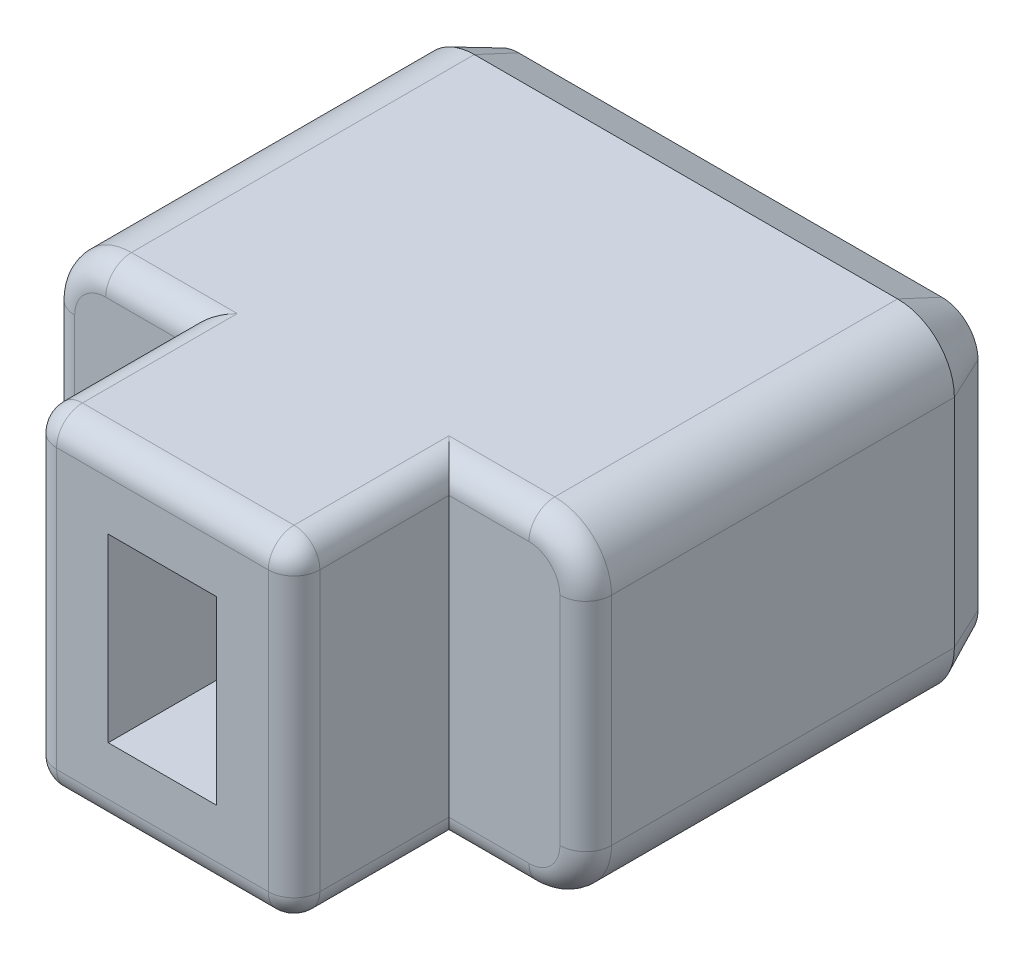
SolidWorks part; units mm, degrees
ref_plane "Plan de face" through (0, 0, 0) normal (0, 0, 1) x (1, 0, 0)
ref_plane "Plan de dessus" through (0, 0, 0) normal (0, 1, 0) x (1, 0, 0)
ref_plane "Plan de droite" through (0, 0, 0) normal (1, 0, 0) x (0, 0, -1)
sketch "Esquisse2" plane through (0, 0, 0) normal (0, 0, 1) x (1, 0, 0)
  line L1 (1.1, 0) -> (9.3, 0)
  line L2 (0, 1.1) -> (0, 5.3)
  line L3 (1.1, 6.4) -> (9.3, 6.4)
  line L4 (10.4, 1.1) -> (10.4, 5.3)
  arc A0 (9.3, 6.4) -> (10.4, 5.3) centre (9.3, 5.3) cw
  arc A1 (9.3, 0) -> (10.4, 1.1) centre (9.3, 1.1) ccw
  arc A2 (1.1, 0) -> (0, 1.1) centre (1.1, 1.1) cw
  arc A3 (0, 5.3) -> (1.1, 6.4) centre (1.1, 5.3) cw
  point P7 (10.4, 6.4)
  point P12 (0, 0)
  point P15 (0, 6.4)
  dimension "D3" = 1.1
  dimension "D1" = 10.4
  dimension "D2" = 6.4
extrude "Boss.-Extru.1" add sketch "Esquisse2" along normal blind 11
sketch "Esquisse3" plane through (0, 0, 11) normal (0, 0, 1) x (1, 0, 0)
  line L0 (0, 5.3) -> (0, 1.1) construction
  line L1 (4.15, 4.95) -> (6.25, 4.95)
  line L2 (4.15, 4.95) -> (4.15, 1.45)
  line L3 (4.15, 1.45) -> (6.25, 1.45)
  line L4 (6.25, 4.95) -> (6.25, 1.45)
  line L5 (10.4, 1.1) -> (10.4, 5.3) construction
  line L6 (9.3, 6.4) -> (1.1, 6.4) construction
  line L7 (1.1, 0) -> (9.3, 0) construction
  dimension "D1" = 2.1
  dimension "D2" = 3.5
  dimension "D3" = 4.15
  dimension "D4" = 4.15
  dimension "D5" = 1.45
  dimension "D6" = 1.45
extrude "Enlèv. mat.-Extru.1" cut sketch "Esquisse3" against normal blind 3
sketch "Esquisse4" plane through (0, 0, 11) normal (0, 0, 1) x (1, 0, 0)
  line L0 (2.65, 6.4) -> (2.65, 0)
  line L1 (9.3, 6.4) -> (1.1, 6.4) construction
  line L2 (1.1, 0) -> (9.3, 0) construction
  line L3 (2.65, 0) -> (7.75, 0)
  line L4 (7.75, 0) -> (7.75, 6.4)
  line L5 (7.75, 6.4) -> (2.65, 6.4)
  line L6 (4.15, 4.95) -> (4.15, 1.45) construction
  line L7 (6.25, 1.45) -> (6.25, 4.95) construction
  dimension "D1" = 1.5
  dimension "D2" = 1.5
extrude "Enlèv. mat.-Extru.2" cut sketch "Esquisse4" against normal blind 3 flip side to cut
fillet "Congé1" radius 0.5 18 edges at (8.525, 0, 8) (10.0778, 0.3222, 8) (10.4, 3.2, 8) (10.0778, 6.0778, 8) (1.875, 6.4, 8) (0.3222, 6.0778, 8) (1.875, 0, 8) (0.3222, 0.3222, 8) (7.75, 6.4, 9.5) (2.65, 6.4, 9.5) (7.75, 0, 9.5) (2.65, 0, 9.5) (2.65, 3.2, 11) (5.2, 6.4, 11) (7.75, 3.2, 11) (5.2, 0, 11) (8.525, 6.4, 8) (0, 3.2, 8)
chamfer "Chanfrein1" distance 0.4 angle 65 8 edges at (5.2, 0, 0) (10.0778, 0.3222, 0) (0.3222, 0.3222, 0) (10.4, 3.2, 0) (0, 3.2, 0) (10.0778, 6.0778, 0) (0.3222, 6.0778, 0) (5.2, 6.4, 0) first distance on face at (5.2, 3.2, 0)
sketch "Esquisse5" plane through (0, 0, 0) normal (0, 0, -1) x (-1, 0, 0)
  line L0 (-0.4, 5.3) -> (-10, 5.3) construction
  arc A0 (-9.3, 6) -> (-10, 5.3) centre (-9.3, 5.3) ccw construction
  text T0 "CLR" font "Century Gothic" height 4
extrude "Enlèv. mat.-Extru.3" cut sketch "Esquisse5" against normal blind 0.3
extrude "Boss.-Extru.2" add sketch "Esquisse5<2>" along normal blind 0.3 separate body
sketch "Esquisse5<2>" plane through (0, 0, 0) normal (0, 0, -1) x (-1, 0, 0) same geometry as "Esquisse5"
